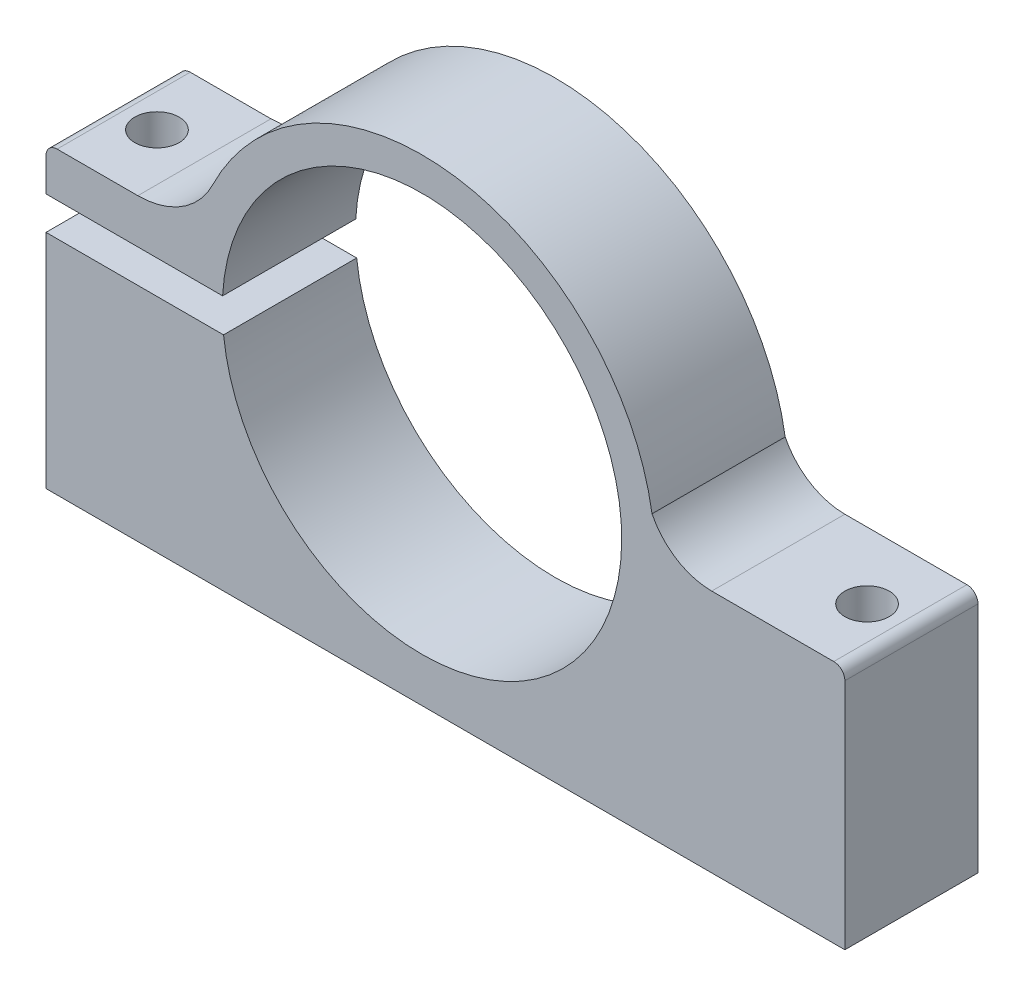
SolidWorks part; units mm, degrees
ref_plane "Front Plane" through (0, 0, 0) normal (0, 0, 1) x (1, 0, 0)
ref_plane "Top Plane" through (0, 0, 0) normal (0, 1, 0) x (1, 0, 0)
ref_plane "Right Plane" through (0, 0, 0) normal (1, 0, 0) x (0, 0, -1)
sketch "Esquisse1" plane through (0, 0, 0) normal (0, 0, 1) x (1, 0, 0)
  line L0 (0, 0) -> (72, 0)
  line L1 (72, 0) -> (72, 22)
  line L2 (15.9163, 23) -> (0, 23)
  line L3 (0, 0) -> (0, 20)
  line L4 (0, 20) -> (16, 20)
  line L5 (0, 23) -> (0, 27)
  line L6 (0, 27) -> (8.276, 27)
  line L7 (72, 22) -> (60, 22)
  arc A0 (16, 20) -> (15.9163, 23) centre (33.8885, 22) ccw
  arc A1 (15.0162, 31.2105) -> (54.6209, 25.3419) centre (33.8885, 22) cw
  arc A2 (60, 22) -> (54.6209, 25.3419) centre (60, 28) cw
  arc A3 (8.276, 27) -> (15.0162, 31.2105) centre (8.276, 34.5) ccw
  dimension "D1" = 20
  dimension "D3" = 22
  dimension "D6" = 3
  dimension "D4" = 18
  dimension "D8" = 0
  dimension "D10" = 3
  dimension "D12" = 7.5
  dimension "D14" = 6
  dimension "D2" = 72
  dimension "D5" = 16
  dimension "D7" = 4
  dimension "D9" = 0
  dimension "D11" = 12
  dimension "D13" = 22
extrude "Boss.-Extru.1" add sketch "Esquisse1" along normal blind 12 contours L4 A0 L2 L5 L6 A3 A1 A2 L7 L1 L0 L3
ref_plane "Plan1" through (0, 0, 0) normal (0, -1, 0) x (-1, 0, 0)
sketch "Esquisse2" plane through (0, 0, 0) normal (0, -1, 0) x (-1, 0, 0)
  line L0 (0, -12) -> (0, 0) construction
  line L1 (-72, -12) -> (-72, 0) construction
  line L3 (0, 0) -> (-72, 0) construction
  circle A0 centre (-4, -6) radius 2
  circle A1 centre (-68, -6) radius 2
  dimension "D1" = 4
  dimension "D2" = 4
  dimension "D4" = 4
  dimension "D6" = 6
  dimension "D3" = 4
  dimension "D5" = 6
extrude "Enlèv. mat.-Extru.2" cut sketch "Esquisse2" against normal through all contours A0
sketch "Esquisse3" plane through (0, 0, 0) normal (0, -1, 0) x (1, 0, 0)
extrude "Enlèv. mat.-Extru.3" cut sketch "Esquisse2<4>" against normal blind 32
sketch "Esquisse2<4>" plane through (0, 0, 0) normal (0, -1, 0) x (-1, 0, 0) same geometry as "Esquisse2"
fillet "Congé1" radius 1 2 edges at (0, 27, 6) (72, 22, 6)
